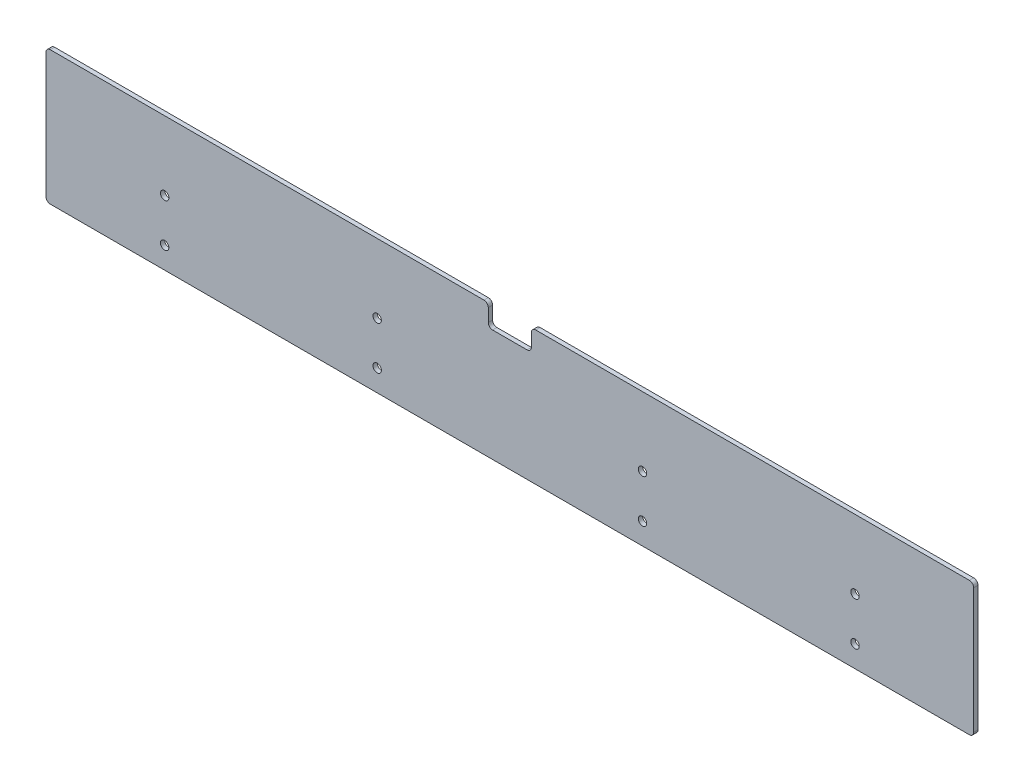
SolidWorks part; units mm, degrees
ref_plane "Front Plane" through (0, 0, 0) normal (0, 0, 1) x (1, 0, 0)
ref_plane "Top Plane" through (0, 0, 0) normal (0, 1, 0) x (1, 0, 0)
ref_plane "Right Plane" through (0, 0, 0) normal (1, 0, 0) x (0, 0, -1)
sketch "Sketch1" plane through (0, 0, 0) normal (0, 0, 1) x (1, 0, 0)
  line L0 (-131.9059, 17.7035) -> (73.0941, 17.7035)
  line L1 (-356.9059, 17.7035) -> (-151.9059, 17.7035)
  line L2 (-356.9059, 17.7035) -> (-356.9059, -44.2965)
  line L3 (-356.9059, -44.2965) -> (73.0941, -44.2965)
  line L4 (73.0941, 17.7035) -> (73.0941, -44.2965)
  line L6 (-151.9059, 17.7035) -> (-151.9059, 7.7035)
  line L7 (-151.9059, 7.7035) -> (-131.9059, 7.7035)
  line L8 (-131.9059, 17.7035) -> (-131.9059, 7.7035)
  circle A0 centre (-80.4059, -14.2965) radius 1.95
  circle A1 centre (-80.4059, -34.2965) radius 1.95
  circle A2 centre (-203.4059, -14.2965) radius 1.95
  circle A3 centre (-203.4059, -34.2965) radius 1.95
  dimension "D3" = 123
  dimension "D4" = 20
  dimension "D1" = 430
  dimension "D2" = 62
  dimension "D5" = 10
  dimension "D6" = 153.5
  dimension "D7" = 20
  dimension "D8" = 10
  dimension "D9" = 205
extrude "Boss-Extrude1" add sketch "Sketch1" along normal blind 2
fillet "Fillet1" radius 2 8 edges at (73.0941, -44.2965, 1) (-356.9059, -44.2965, 1) (-356.9059, 17.7035, 1) (-151.9059, 7.7035, 1) (-151.9059, 17.7035, 1) (-131.9059, 7.7035, 1) (-131.9059, 17.7035, 1) (73.0941, 17.7035, 1)
sketch "Sketch2" plane through (0, 0, 2) normal (0, 0, 1) x (1, 0, 0)
  line L0 (-354.9059, -44.2965) -> (71.0941, -44.2965) construction
  line L1 (-356.9059, 15.7035) -> (-356.9059, -42.2965) construction
  line L2 (73.0941, -42.2965) -> (73.0941, 15.7035) construction
  circle A0 centre (-301.9059, -14.2965) radius 1.95
  circle A1 centre (-301.9059, -34.2965) radius 1.95
  circle A2 centre (18.0941, -14.2965) radius 1.95
  circle A3 centre (18.0941, -34.2965) radius 1.95
  dimension "D1" = 20
  dimension "D2" = 10
  dimension "D3" = 55
  dimension "D4" = 55
  dimension "D5" = 20
  dimension "D6" = 10
extrude "Cut-Extrude1" cut sketch "Sketch2" against normal blind 10
